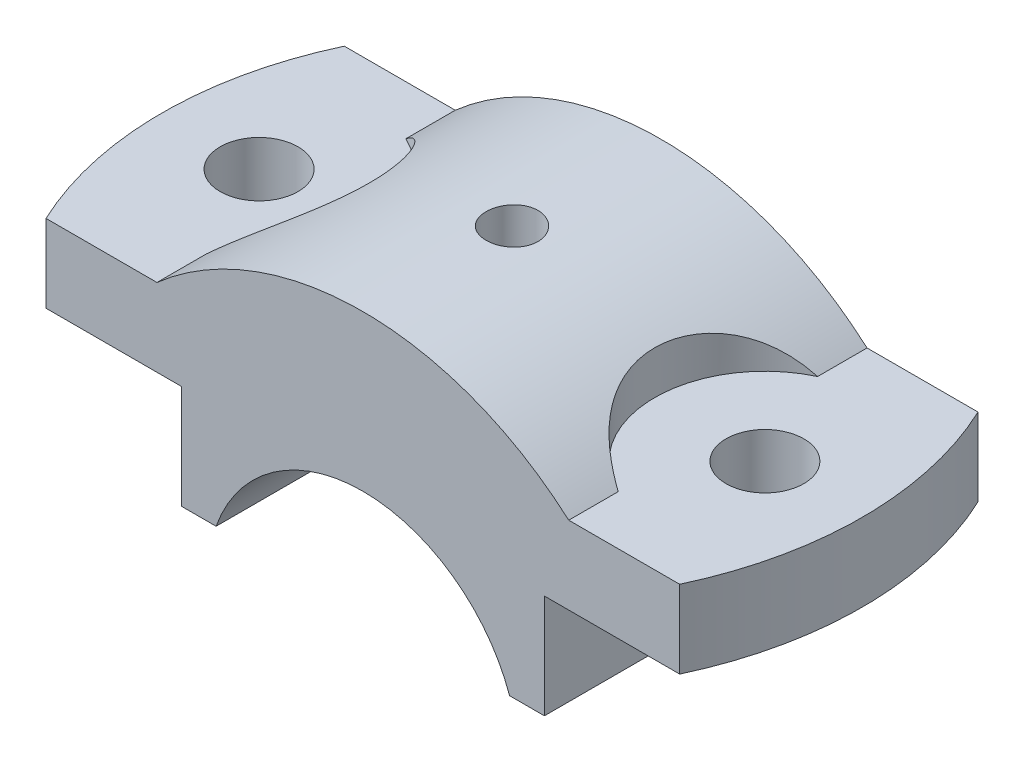
SolidWorks part; units mm, degrees
ref_plane "Front Plane" through (0, 0, 0) normal (0, 0, 1) x (1, 0, 0)
ref_plane "Top Plane" through (0, 0, 0) normal (0, 1, 0) x (1, 0, 0)
ref_plane "Right Plane" through (0, 0, 0) normal (1, 0, 0) x (0, 0, -1)
sketch "Sketch1" plane through (0, 0, 0) normal (0, 0, 1) x (1, 0, 0)
  line L0 (-28, 24) -> (-54, 24)
  line L1 (-54, 24) -> (-54, 36)
  line L2 (-54, 36) -> (-31.749, 36)
  line L3 (31.749, 36) -> (54, 36)
  line L4 (54, 36) -> (54, 24)
  line L5 (54, 24) -> (28, 24)
  line L6 (28, 24) -> (28, 8)
  line L7 (28, 8) -> (22.6274, 8)
  line L8 (-22.6274, 8) -> (-28, 8)
  line L9 (-28, 8) -> (-28, 24)
  arc A0 (-31.749, 36) -> (31.749, 36) centre (0, 0) cw
  arc A1 (22.6274, 8) -> (-22.6274, 8) centre (0, 0) ccw
  dimension "D1" = 48
  dimension "D2" = 48
  dimension "D3" = 12
  dimension "D4" = 56
  dimension "D5" = 108
  dimension "D6" = 8
  dimension "D7" = 16
extrude "Boss-Extrude1" add sketch "Sketch1" along normal mid plane 46
sketch "Sketch3" plane through (0, 36, 0) normal (0, 1, 0) x (1, 0, 0)
  line L0 (-31.749, -23) -> (-31.749, 23) construction
  line L1 (-31.749, -15.3761) -> (-31.749, 15.3761)
  line L2 (-31.749, -23) -> (-54, -23) construction
  line L3 (-31.749, 23) -> (-54, 23) construction
  line L4 (-54, -23) -> (-54, 23) construction
  line L5 (-48.8569, -23) -> (-54, -23)
  line L6 (-54, -23) -> (-54, 23)
  line L7 (-48.8569, 23) -> (-54, 23)
  circle A0 centre (-39, 0) radius 6
  arc A1 (-48.8569, -23) -> (-48.8569, 23) centre (0, 0) cw
  arc A2 (-31.749, 15.3761) -> (-31.749, -15.3761) centre (-39, 0) cw
  line M1 (-31.749, 23) -> (-54, 23)
  line M2 (-54, 23) -> (-54, -23)
  line M3 (-54, -23) -> (-31.749, -23)
  line M4 (-31.749, -23) -> (-31.749, 23)
  dimension "D2" = 12
  dimension "D3" = 54
  dimension "D4" = 17
  dimension "D1" = 39
extrude "Cut-Extrude1" cut sketch "Sketch3" against normal through all contours A0 | A1 M2 M1 | A1 L6 M3 region at (-52.4705, 36, -17.3062) region at (-52.4705, 36, 17.3062) region at (-39, 36, 0)
extrude "Cut-Extrude3" cut sketch "Sketch3<3>" along normal through all contours A2 M4 region at (-27.7342, 36, 0)
sketch "Sketch3<3>" plane through (0, 36, 0) normal (0, 1, 0) x (1, 0, 0) same geometry as "Sketch3"
mirror "Mirror1" about plane through (0, 0, 0) normal (1, 0, 0) of "Cut-Extrude3", "Cut-Extrude1"
sketch "Sketch9" plane through (0, 0, 0) normal (0, 0, 1) x (1, 0, 0)
  line L0 (0, 48) -> (4, 48)
  line L1 (4, 48) -> (4, 32)
  line L2 (3, 32) -> (3, 23.8118)
  line L3 (3, 23.8118) -> (0, 23.8118)
  line L4 (0, 23.8118) -> (0, 48)
  line L5 (4, 32) -> (3, 32)
  arc A0 (31.749, 36) -> (-31.749, 36) centre (0, 0) ccw construction
  arc A1 (22.6274, 8) -> (-22.6274, 8) centre (0, 0) ccw construction
  point P5 (0, 0)
  dimension "D1" = 16
  dimension "D2" = 4
  dimension "D3" = 3
revolve "Cut-Revolve1" cut sketch "Sketch9" angle 360 about L4
